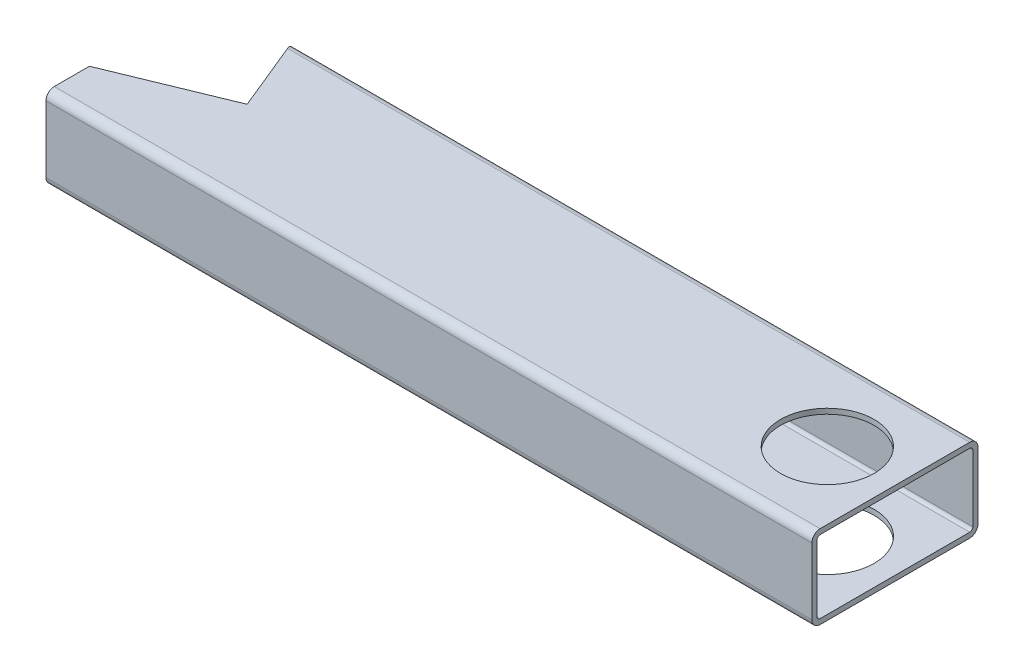
SolidWorks part; units mm, degrees
material "6061 Alloy"
ref_plane "Front" through (0, 0, 0) normal (0, 0, 1) x (1, 0, 0)
ref_plane "Top" through (0, 0, 0) normal (0, 1, 0) x (1, 0, 0)
ref_plane "Right" through (0, 0, 0) normal (1, 0, 0) x (0, 0, -1)
sketch "Sketch1" plane through (0, 0, 0) normal (1, 0, 0) x (0, 0, -1)
  line L1 (-2.54, 0) -> (-48.26, 0)
  line L2 (0, 2.54) -> (0, 22.86)
  line L3 (-2.54, 25.4) -> (-48.26, 25.4)
  line L4 (-50.8, 2.54) -> (-50.8, 22.86)
  arc A0 (-50.8, 2.54) -> (-48.26, 0) centre (-48.26, 2.54) ccw
  arc A1 (-2.54, 0) -> (0, 2.54) centre (-2.54, 2.54) ccw
  arc A2 (0, 22.86) -> (-2.54, 25.4) centre (-2.54, 22.86) ccw
  arc A3 (-48.26, 25.4) -> (-50.8, 22.86) centre (-48.26, 22.86) ccw
  point P7 (-50.8, 0)
  point P10 (0, 0)
  point P13 (0, 25.4)
  dimension "D3" = 2.54
  dimension "D1" = 25.4
  dimension "D2" = 50.8
extrude "Extrude-Thin1" add sketch "Sketch1" against normal blind 243.6368 thin thin type one direction reverse wall 1.5875
sketch "Sketch3" plane through (0, 25.4, 0) normal (0, 1, 0) x (1, 0, 0)
  line L0 (0, 49.2125) -> (79.6022, 243.0747)
  line L1 (0, -1.5875) -> (25.4, -1.5875)
  line L2 (0, -1.5875) -> (0, 49.2125)
  line L3 (0, 49.2125) -> (25.4, 49.2125)
  line L4 (25.4, -1.5875) -> (25.4, 49.2125)
  line L5 (79.6022, 243.0747) -> (126.5949, 223.7789)
  line L6 (126.5949, 223.7789) -> (34.0567, -1.5875)
  line L7 (71.7537, 223.9604) -> (118.7463, 204.6646) construction
  line L8 (95.25, 214.3125) -> (0, 214.3125)
  line L9 (0, 49.2125) -> (0, 289.0515)
  line L10 (25.4, -1.5875) -> (34.0567, -1.5875)
  circle A0 centre (95.25, 214.3125) radius 14.3129
  point P11 (95.25, 214.3125)
  dimension "D4" = 28.6258
  dimension "D5" = 6.35
  dimension "D1" = 25.4
  dimension "D2" = 50.8
  dimension "D3" = 50.8
  dimension "D6" = 95.25
  dimension "D7" = 165.1
  dimension "D8" = 243.6254
  dimension "D9" = 209.5687
sketch "Sketch4" plane through (0, 25.4, 0) normal (0, 1, 0) x (1, 0, 0)
  line L0 (-20.6629, -48.26) -> (-20.6629, -2.54) construction
  line L1 (-234.1118, -37.5373) -> (-234.1118, -50.8)
  line L2 (-243.6368, -2.54) -> (0, -2.54) construction
  line L3 (-243.6368, -48.26) -> (0, -48.26) construction
  line L4 (0, -2.54) -> (0, -48.26) construction
  line L5 (0, 0) -> (-209.5754, 0) construction
  line L6 (-243.6368, 0) -> (0, 0) construction
  line L7 (-209.5754, 0) -> (-199.9249, -23.4953)
  line L8 (-199.9249, -23.4953) -> (-234.1118, -37.5373)
  line L9 (-243.6368, -50.8) -> (0, -50.8) construction
  line L11 (-209.5754, 0) -> (-243.6368, 0)
  line L12 (-243.6368, 0) -> (-243.6368, -50.8)
  line L14 (-234.1118, -50.8) -> (-243.6368, -50.8)
  circle A0 centre (-20.6629, -25.4) radius 14.3129
  point P5 (-20.6629, -25.4)
  point P22 (-243.6368, -36.3557)
  point P24 (0, 0)
  point P28 (0, 0)
  point P29 (-243.6368, -50.2727)
  dimension "D1" = 28.6258
  dimension "D2" = 6.35
  dimension "D3" = 25.4
  dimension "D4" = 209.5754
  dimension "D5" = 67.67
  dimension "D6" = 9.525
extrude "Cut-Extrude1" cut sketch "Sketch4" against normal through all and the other way through all
